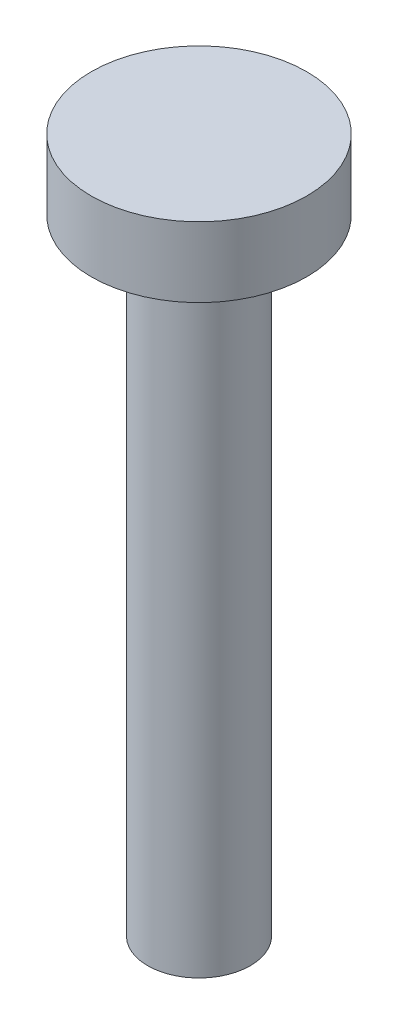
SolidWorks part; units mm, degrees
material "Brass"
ref_plane "Front Plane" through (0, 0, 0) normal (0, 0, 1) x (1, 0, 0)
ref_plane "Top Plane" through (0, 0, 0) normal (0, 1, 0) x (1, 0, 0)
ref_plane "Right Plane" through (0, 0, 0) normal (1, 0, 0) x (0, 0, -1)
sketch "Sketch1" plane through (0, 0, 0) normal (0, 0, 1) x (1, 0, 0)
  line L0 (0, 0) -> (0, 64.5) construction
  line L1 (0, 0) -> (4.7625, 0)
  line L2 (4.7625, 0) -> (4.7625, 58)
  line L3 (4.7625, 58) -> (10, 58)
  line L4 (10, 58) -> (10, 64.5)
  line L5 (10, 64.5) -> (0, 64.5)
  line L6 (0, 64.5) -> (0, 0)
  dimension "D1" = 4.7625
  dimension "D2" = 58
  dimension "D3" = 5.2375
  dimension "D4" = 6.5
revolve "Revolve1" add sketch "Sketch1" angle 360 about L0
